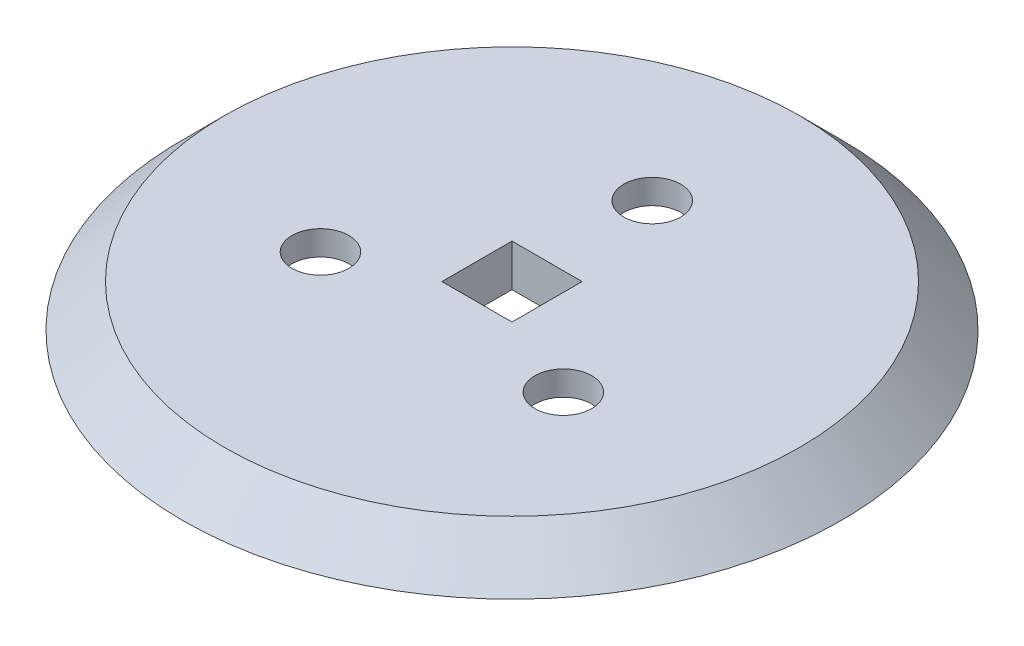
SolidWorks part; units mm, degrees
ref_plane "Front" through (0, 0, 0) normal (0, 0, 1) x (1, 0, 0)
ref_plane "Top" through (0, 0, 0) normal (0, 1, 0) x (1, 0, 0)
ref_plane "Right" through (0, 0, 0) normal (1, 0, 0) x (0, 0, -1)
sketch "Sketch1" plane through (0, 0, 0) normal (0, 1, 0) x (1, 0, 0)
  line L0 (0, 0) -> (0, 12.7) construction
  line L1 (-3.175, 3.175) -> (3.175, 3.175)
  line L2 (-3.175, 3.175) -> (-3.175, -3.175)
  line L3 (-3.175, -3.175) -> (3.175, -3.175)
  line L4 (3.175, 3.175) -> (3.175, -3.175)
  line L5 (0, 0) -> (10.9985, -6.35) construction
  line L6 (0, 0) -> (-10.9985, -6.35) construction
  circle A0 centre (0, 0) radius 31.75
  circle A1 centre (0, 12.7) radius 2.5797
  circle A2 centre (10.9985, -6.35) radius 2.5797
  circle A3 centre (-10.9985, -6.35) radius 2.5797
  point P9 (0, 3.175)
  point P10 (3.175, 0)
  point P17 (0, 0)
  dimension "D1" = 63.5
  dimension "D4" = 5.1594
  dimension "D2" = 6.35
  dimension "D3" = 12.7
  dimension "D5" = 3
extrude "Boss-Extrude1" add sketch "Sketch1" along normal blind 3.81
chamfer "Chamfer1" distance 5.715 angle 45 1 edges at (0, 3.81, 31.75)
sketch "Sketch2" plane through (0, 0, 0) normal (0, -1, 0) x (-1, 0, 0)
  circle A0 centre (0, 12.7) radius 5.4094
  circle A1 centre (10.9985, -6.35) radius 5.4094
  circle A2 centre (-10.9985, -6.35) radius 5.4094
  dimension "D1" = 10.8188
extrude "Cut-Extrude1" cut sketch "Sketch2" against normal blind 1.5875
